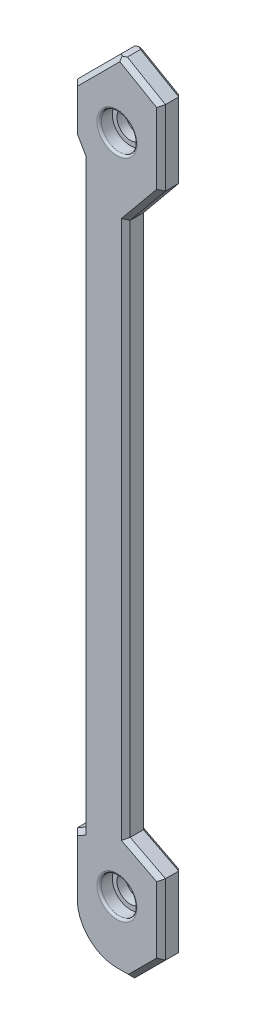
SolidWorks part; units mm, degrees
ref_plane "前视基准面" through (0, 0, 0) normal (0, 0, 1) x (1, 0, 0)
ref_plane "上视基准面" through (0, 0, 0) normal (0, 1, 0) x (1, 0, 0)
ref_plane "右视基准面" through (0, 0, 0) normal (1, 0, 0) x (0, 0, -1)
other "Configuration Table"
sketch "草图1" plane through (0, 0, 0) normal (0, 0, 1) x (1, 0, 0)
  line L0 (0, 86.6243) -> (0, -53.6692) construction
  line L1 (-10, -90) -> (10, -90)
  line L2 (-10, -90) -> (-10, 90)
  line L3 (-10, 90) -> (10, 90)
  line L4 (10, -90) -> (10, 90)
  line L5 (-10, -90) -> (10, 90) construction
  line L6 (-10, 90) -> (10, -90) construction
  circle A0 centre (0, -75) radius 3
  circle A1 centre (0, 75) radius 3
  point P0 (0, 0)
  dimension "D5" = 6
  dimension "D6" = 6
  dimension "D1" = 180
  dimension "D2" = 20
  dimension "D3" = 150
  dimension "D4" = 15
extrude "凸台-拉伸1" add sketch "草图1" along normal blind 5
sketch "草图2" plane through (0, 0, 5) normal (0, 0, 1) x (1, 0, 0)
  circle A0 centre (0, 75) radius 4.05
  circle A1 centre (0, -75) radius 4.05
  dimension "D1" = 8.1
  dimension "D2" = 8.1
extrude "切除-拉伸1" cut sketch "草图2" against normal blind 3
chamfer "倒角1" distance 10 angle 45 1 edges at (-10, 90, 2.5)
chamfer "倒角2" distance 5 angle 60 1 edges at (10, 90, 2.5) first distance on face at (10, 0, 2.5)
sketch "草图3" plane through (0, 0, 5) normal (0, 0, 1) x (1, 0, 0)
  line L0 (10, 68) -> (2, 58.2683)
  line L1 (10, -90) -> (10, 85) construction
  line L2 (2, 58.2683) -> (2, -62.881)
  line L3 (2, -62.881) -> (10, -67)
  line L4 (10, -67) -> (10, 68)
  dimension "D1" = 17
  dimension "D2" = 8
  dimension "D3" = 135
extrude "切除-拉伸2" cut sketch "草图3" against normal blind 10
fillet "圆角1" radius 10 1 edges at (-10, -90, 2.5)
chamfer "倒角3" distance 7 angle 45 1 edges at (10, -90, 2.5)
chamfer "倒角5" distance 1 angle 45 16 edges at (-5, 85, 0) (-5, 85, 5) (5.6699, 87.5, 0) (6.5, -86.5, 0) (10, -75, 0) (6, -64.9405, 0) (10, 76.5, 0) (6, 63.1341, 0) (2, -2.3064, 0) (5.6699, 87.5, 5) (6.5, -86.5, 5) (10, -75, 5) (6, -64.9405, 5) (10, 76.5, 5) (6, 63.1341, 5) (2, -2.3064, 5)
sketch "草图4" plane through (0, 0, 5) normal (0, 0, 1) x (1, 0, 0)
  line L0 (-10, 70) -> (-8, 66.5359)
  line L1 (-10, 78.5858) -> (-10, -80) construction
  line L2 (-8, 66.5359) -> (-8, -65.8453)
  line L3 (-8, -65.8453) -> (-10, -67)
  line L4 (-10, -67) -> (-10, 70)
  dimension "D1" = 2
  dimension "D2" = 10
  dimension "D3" = 137
  dimension "D4" = 30
extrude "切除-拉伸3" cut sketch "草图4" against normal blind 10
chamfer "倒角6" distance 1 angle 45 14 edges at (-9, -66.4226, 0) (-10, 74.2929, 0) (-9, 68.2679, 0) (-8, 0.3453, 0) (0.7929, -90, 0) (-10, -73.5, 0) (-7.0711, -87.0711, 0) (0.7929, -90, 5) (-7.0711, -87.0711, 5) (-10, 74.2929, 5) (-9, 68.2679, 5) (-8, 0.3453, 5) (-9, -66.4226, 5) (-10, -73.5, 5)
fillet "圆角2" radius 0.5 1 edges at (4.05, -75, 5)
fillet "圆角3" radius 0.5 1 edges at (4.05, 75, 5)
